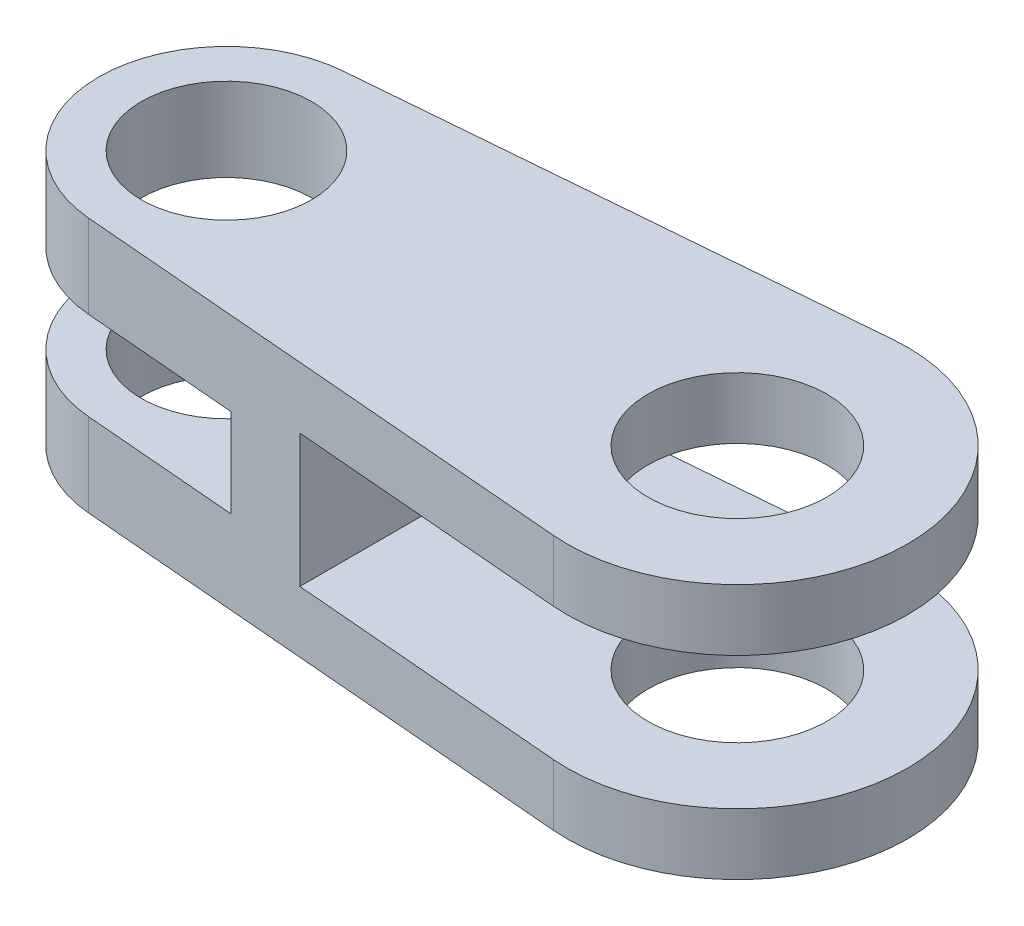
SolidWorks part; units mm, degrees
ref_plane "XY" through (0, 0, 0) normal (0, 0, 1) x (1, 0, 0)
ref_plane "XZ" through (0, 0, 0) normal (0, 1, 0) x (1, 0, 0)
ref_plane "YZ" through (0, 0, 0) normal (1, 0, 0) x (0, 0, -1)
ref_axis "X" through (-13.1762, 0, 0) along (1, 0, 0)
ref_axis "Y" through (0, -10.4775, 0) along (0, 1, 0)
ref_axis "Z" through (0, 0, 13.97) along (0, 0, -1)
sketch "Sketch1" plane through (0, 0, 0) normal (0, 1, 0) x (1, 0, 0)
  line L0 (-0.7937, 9.4919) -> (37.0417, 12.6558)
  line L1 (37.0417, -12.6558) -> (-0.7937, -9.4919)
  line L2 (0, 0) -> (38.1, 0) construction
  arc A0 (37.0417, 12.6558) -> (37.0417, -12.6558) centre (38.1, 0) cw
  arc A1 (-0.7937, -9.4919) -> (-0.7937, 9.4919) centre (0, 0) cw
  circle A3 centre (0, 0) radius 6.35
  circle A4 centre (38.1, 0) radius 6.6675
  dimension "D1" = 9.525
  dimension "D2" = 13.335
  dimension "D3" = 12.7
  dimension "D4" = 12.7
  dimension "D5" = 38.1
extrude "Boss-Extrude1" add sketch "Sketch1" along normal mid plane 19.05
sketch "Sketch2" plane through (0, 0, 0) normal (0, 1, 0) x (1, 0, 0)
  line L0 (37.0417, 12.6558) -> (-0.7937, 9.4919) construction
  line L1 (-10.795, -10.461) -> (10.795, -10.461)
  line L2 (-10.795, -10.461) -> (-10.795, 10.461)
  line L3 (-10.795, 10.461) -> (10.795, 10.461)
  line L4 (10.795, -10.461) -> (10.795, 10.461)
  line L5 (-10.795, -10.461) -> (10.795, 10.461) construction
  line L6 (-10.795, 10.461) -> (10.795, -10.461) construction
  point P0 (0, 0)
  dimension "D1" = 10.795
extrude "Cut-Extrude1" cut sketch "Sketch2" against normal mid plane 6.604
sketch "Sketch3" plane through (0, 0, 0) normal (0, 1, 0) x (1, 0, 0)
  line L0 (0, 0) -> (16.4, 0) construction
  line L1 (37.0417, 12.6558) -> (16.4, 10.9297)
  line L3 (37.0417, -12.6558) -> (16.4, -10.9297)
  line L4 (16.4, 10.9297) -> (16.4, -10.9297)
  line L5 (37.0417, 12.6558) -> (-0.7937, 9.4919) construction
  line L6 (-0.7937, -9.4919) -> (37.0417, -12.6558) construction
  arc A0 (37.0417, -12.6558) -> (37.0417, 12.6558) centre (38.1, 0) ccw construction
  arc A2 (37.0417, -12.6558) -> (37.0417, 12.6558) centre (38.1, 0) ccw
  dimension "D1" = 21.7
extrude "Cut-Extrude2" cut sketch "Sketch3" against normal mid plane 9.906
